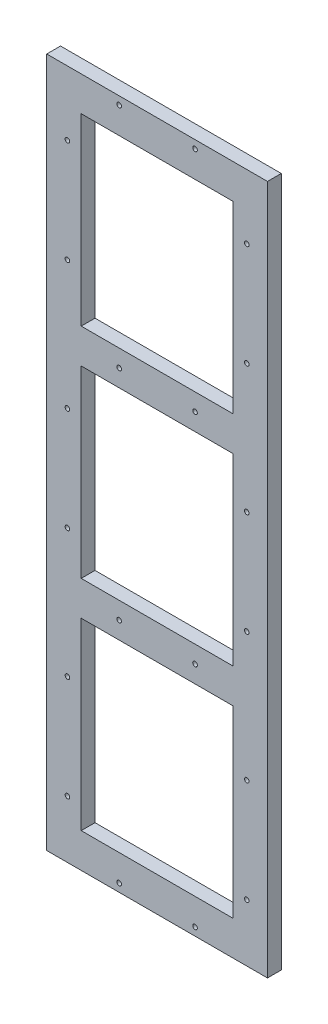
SolidWorks part; units mm, degrees
material "Alumina"
ref_plane "Front Plane" through (0, 0, 0) normal (0, 0, 1) x (1, 0, 0)
ref_plane "Top Plane" through (0, 0, 0) normal (0, 1, 0) x (1, 0, 0)
ref_plane "Right Plane" through (0, 0, 0) normal (1, 0, 0) x (0, 0, -1)
sketch "Sketch1" plane through (0, 0, 0) normal (0, 0, 1) x (1, 0, 0)
  line L0 (33, 141) -> (33, 61)
  line L9 (-48, -144) -> (48, -144)
  line L10 (-48, -144) -> (-48, 156)
  line L11 (-48, 156) -> (48, 156)
  line L12 (48, -144) -> (48, 156)
  line L14 (0, 0) -> (0, 46) construction
  line L15 (-33, -129) -> (33, -129)
  line L17 (-33, 141) -> (33, 141)
  line L19 (-33, 46) -> (-33, -34)
  line L20 (-33, -49) -> (-33, -129)
  line L21 (-33, 61) -> (33, 61)
  line L23 (-33, 46) -> (33, 46)
  line L25 (-33, -34) -> (33, -34)
  line L27 (-33, -49) -> (33, -49)
  line L33 (33, 46) -> (33, -34)
  line L34 (-33, 61) -> (-33, 141)
  line L36 (33, -49) -> (33, -129)
  dimension "D1" = 96
  dimension "D2" = 15
  dimension "D3" = 66
  dimension "D4" = 80
  dimension "D5" = 15
  dimension "D6" = 80
  dimension "D7" = 15
  dimension "D8" = 80
  dimension "D9" = 46
  dimension "D10" = 15
  dimension "D12" = 15
extrude "Boss-Extrude1" add sketch "Sketch1" along normal blind 6
sketch "Sketch3" plane through (0, 0, 6) normal (0, 0, 1) x (1, 0, 0)
  line L0 (48, 156) -> (-48, 156) construction
  line L1 (-48, 156) -> (-48, -144) construction
  line L2 (-39, 128) -> (39, 128) construction
  line L3 (-16.5, 152.5) -> (-16.5, 53.5) construction
  line L4 (-39, 128) -> (-39, 83) construction
  line L5 (-39, 128) -> (-39, 27) construction
  circle A0 centre (-39, 128) radius 1
  circle A12 centre (-16.5, 152.5) radius 1
  circle A19 centre (16.5, 152.5) radius 1
  circle A20 centre (-16.5, 53.5) radius 1
  circle A21 centre (16.5, 53.5) radius 1
  circle A26 centre (-39, 27) radius 1
  circle A27 centre (39, 128) radius 1
  circle A28 centre (39, 83) radius 1
  circle A29 centre (-39, 83) radius 1
  circle A30 centre (39, 27) radius 1
  circle A31 centre (39, -18) radius 1
  circle A32 centre (-39, -18) radius 1
  circle A33 centre (-39, -74) radius 1
  circle A34 centre (39, -74) radius 1
  circle A35 centre (39, -119) radius 1
  circle A36 centre (-39, -119) radius 1
  dimension "D1" = 28
  dimension "D6" = 2
  dimension "D3" = 2
  dimension "D8" = 3.5
  dimension "D9" = 33
  dimension "D10" = 31.5
  dimension "D12" = 2
  dimension "D13" = 45
  dimension "D14" = 9
  dimension "D2" = 78
  dimension "D7" = 3.5
  dimension "D11" = 99
  dimension "D16" = 101
  dimension "D17" = 2
  dimension "D4" = 2
  dimension "D5" = 2
  dimension "D15" = 3
extrude "Cut-Extrude6" cut sketch "Sketch3" against normal blind 10
ref_plane "Plane1" through (0, 6, 0) normal (0, 1, 0) x (1, 0, 0)
sketch "Sketch4" plane through (0, 0, 6) normal (0, 0, 1) x (1, 0, 0)
  line L1 (3.3, 6) -> (-3.3, 6) construction
  circle A1 centre (16.5, -41.5) radius 1
  circle A3 centre (-16.5, -41.5) radius 1
  circle A4 centre (16.5, 152.5) radius 1
  circle A5 centre (-16.5, 152.5) radius 1
  circle A6 centre (-16.5, 152.5) radius 1
  circle A7 centre (-16.5, 53.5) radius 1
  circle A8 centre (16.5, 53.5) radius 1
  circle A9 centre (-16.5, -140.5) radius 1
  circle A10 centre (16.5, -140.5) radius 1
  dimension "D2" = 2
  dimension "D3" = 2
  dimension "D4" = 2
  dimension "D1" = 0
extrude "Cut-Extrude8" cut sketch "Sketch4" against normal blind 10
